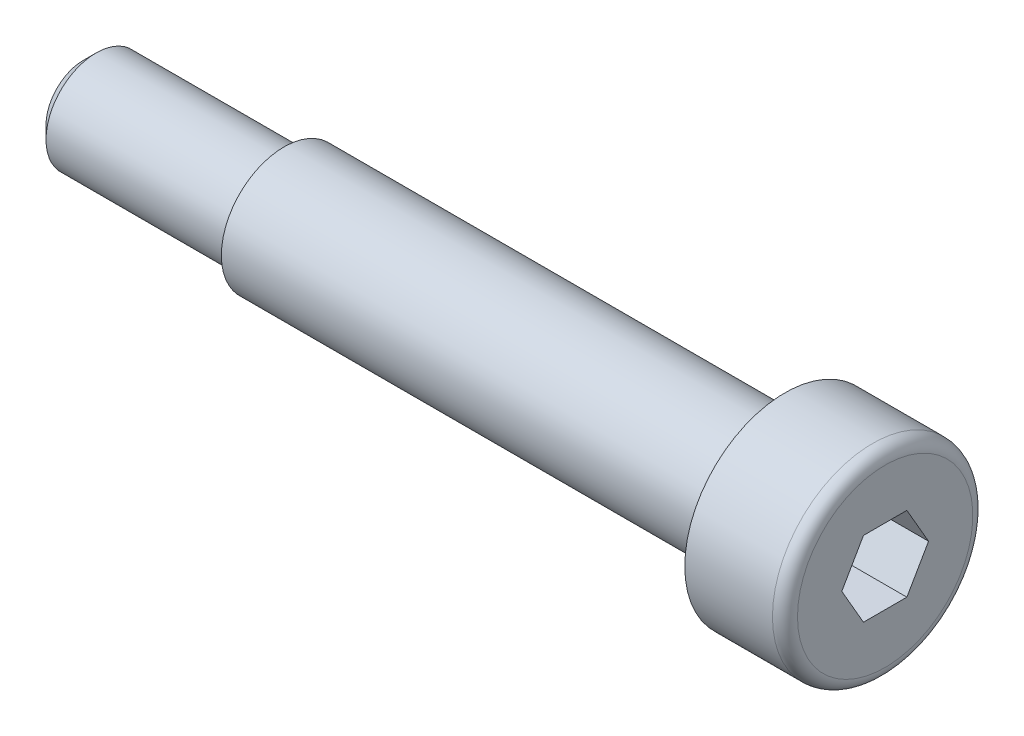
SolidWorks part; units mm, degrees
material "AISI 1020"
ref_plane "XY (Front)" through (0, 0, 0) normal (0, 0, 1) x (1, 0, 0)
ref_plane "XZ (Top)" through (0, 0, 0) normal (0, 1, 0) x (1, 0, 0)
ref_plane "YZ (Right)" through (0, 0, 0) normal (1, 0, 0) x (0, 0, -1)
ref_axis "X" through (-25.2, 0, 0) along (1, 0, 0)
ref_axis "Y" through (0, 5.5, 0) along (0, -1, 0)
ref_axis "Z" through (0, 0, -5.5) along (0, 0, 1)
sketch "Sketch1" plane through (0, 0, 0) normal (0, 0, 1) x (1, 0, 0)
  line L0 (0, 0) -> (0, 3.5)
  line L1 (-0.5, 4) -> (-4, 4)
  line L2 (-4, 4) -> (-4, 2.5)
  line L3 (-4, 2.5) -> (-24, 2.5)
  line L4 (-24, 2.5) -> (-24, 2)
  line L5 (-24, 2) -> (-32, 2)
  line L6 (-32, 2) -> (-32, 0)
  line L7 (-32, 0) -> (0, 0)
  line L8 (0, 0) -> (5.7531, 0) construction
  arc A0 (0, 3.5) -> (-0.5, 4) centre (-0.5, 3.5) ccw
  dimension "R" = 0.5
  dimension "d3" = 8
  dimension "d1" = 5
  dimension "M" = 4
  dimension "l3" = 4
  dimension "l1" = 20
  dimension "l2" = 8
revolve "Revolve1" add sketch "Sketch1" angle 360 about L8
chamfer "Chamfer1" distance 0.5 angle 45 1 edges at (-32, 0, 2)
sketch "Sketch2" plane through (0, 0, 0) normal (1, 0, 0) x (0, 0, -1)
  line L1 (1.7321, 0) -> (0.866, 1.5)
  line L2 (0.866, 1.5) -> (-0.866, 1.5)
  line L3 (-0.866, 1.5) -> (-1.7321, 0)
  line L4 (-1.7321, 0) -> (-0.866, -1.5)
  line L5 (-0.866, -1.5) -> (0.866, -1.5)
  line L6 (0.866, -1.5) -> (1.7321, 0)
  circle A0 centre (0, 0) radius 1.5 construction
  dimension "AF" = 3
extrude "Cut-Extrude1" cut sketch "Sketch2" against normal blind 2.4
